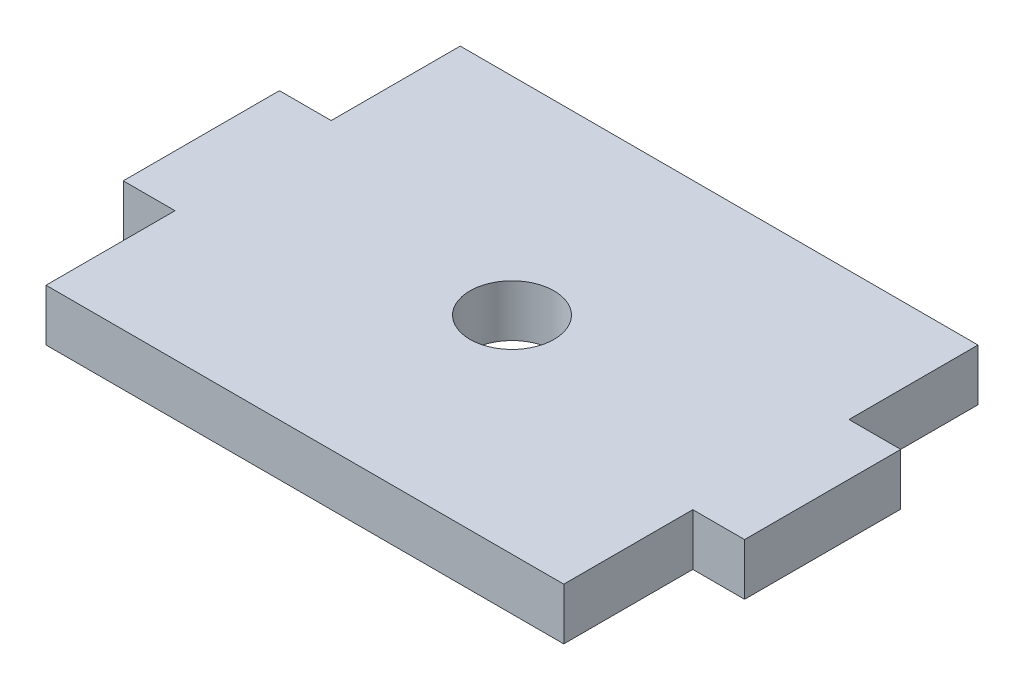
SolidWorks part; units mm, degrees
ref_plane "Front Plane" through (0, 0, 0) normal (0, 0, 1) x (1, 0, 0)
ref_plane "Top Plane" through (0, 0, 0) normal (0, 1, 0) x (1, 0, 0)
ref_plane "Right Plane" through (0, 0, 0) normal (1, 0, 0) x (0, 0, -1)
sketch "Sketch1" plane through (0, 0, 0) normal (0, 1, 0) x (1, 0, 0)
  line L0 (-15.875, -4.7879) -> (-15.875, -12.7)
  line L1 (-15.875, 12.7) -> (15.875, 12.7)
  line L2 (-15.875, 12.7) -> (-15.875, 4.7879)
  line L3 (-15.875, -12.7) -> (15.875, -12.7)
  line L4 (15.875, 12.7) -> (15.875, 4.7879)
  line L5 (-15.875, 12.7) -> (15.875, -12.7) construction
  line L6 (-15.875, -12.7) -> (15.875, 12.7) construction
  line L7 (15.875, 4.7879) -> (19.05, 4.7879)
  line L9 (15.875, -4.7879) -> (19.05, -4.7879)
  line L10 (19.05, 4.7879) -> (19.05, -4.7879)
  line L11 (-19.05, 0) -> (19.05, 0) construction
  line L13 (-19.05, 4.7879) -> (-15.875, 4.7879)
  line L14 (-19.05, 4.7879) -> (-19.05, -4.7879)
  line L15 (-19.05, -4.7879) -> (-15.875, -4.7879)
  line L19 (15.875, -4.7879) -> (15.875, -12.7)
  circle A0 centre (0, 0) radius 2.5797
  point P0 (0, 0)
  dimension "D6" = 5.1594
  dimension "D1" = 25.4
  dimension "D2" = 3.175
  dimension "D3" = 9.5758
  dimension "D4" = 31.75
  dimension "D5" = 3.175
extrude "Boss-Extrude1" add sketch "Sketch1" along normal mid plane 3.175 contours L19 L9 L10 L7 L4 L1 L2 L13 L14 L15 L0 L3 A0 region at (-17.4625, 0, 4.33)
equation "\"D3@Sketch1\"=0.375in+0.002in"
